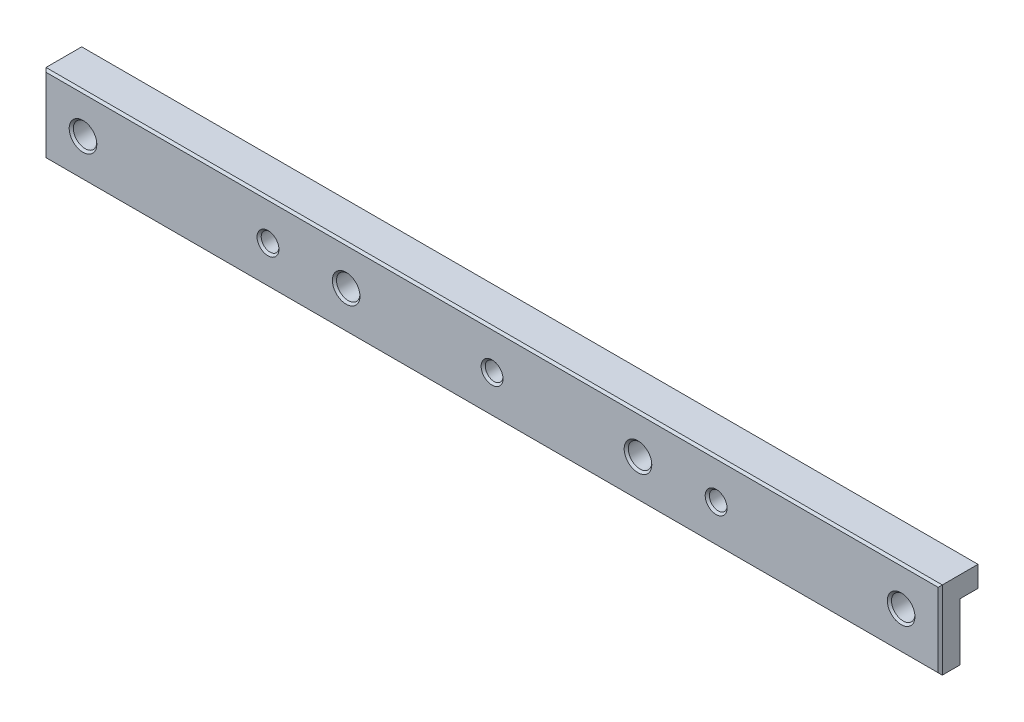
SolidWorks part; units mm, degrees
ref_plane "Front Plane" through (0, 0, 0) normal (0, 0, 1) x (1, 0, 0)
ref_plane "Top Plane" through (0, 0, 0) normal (0, 1, 0) x (1, 0, 0)
ref_plane "Right Plane" through (0, 0, 0) normal (1, 0, 0) x (0, 0, -1)
sketch "Sketch1" plane through (0, 0, 0) normal (0, 0, 1) x (1, 0, 0)
  line L0 (0, 7.5) -> (0, 0) construction
  line L1 (86, 7.5) -> (-86, 7.5)
  line L2 (86, 7.5) -> (86, 3.5)
  line L3 (86, -7.5) -> (-86, -7.5)
  line L4 (-86, 7.5) -> (-86, 3.5)
  line L5 (86, 3.5) -> (-86, 3.5)
  line L6 (-86, 3.5) -> (-86, -7.5)
  line L7 (86, 3.5) -> (86, -7.5)
  line L8 (0, 0) -> (0, -7.5) construction
  dimension "D1" = 172
  dimension "D2" = 7.5
  dimension "D3" = 4
extrude "Boss-Extrude1" add sketch "Sketch1" against normal blind 7.25 contours L7 L5 L6 L3 | L1 L0 L5 L2 | L0 L1 L4 L5 region at (0, 5.5, 0) region at (0, -2, 0)
extrude "Cut-Extrude1" cut sketch "Sketch1<6>" along normal blind 3.5 from surface contours L7 L5 L6 L3 region at (0, -2, 0) starting at face at (0, 0, -7.25)
sketch "Sketch1<6>" plane through (0, 0, 0) normal (0, 0, 1) x (1, 0, 0) same geometry as "Sketch1"
sketch "Sketch2" plane through (0, 0, 0) normal (0, 0, 1) x (1, 0, 0)
  line L0 (78.5, 0) -> (0, 0) construction
  line L1 (-86, 3.5) -> (-86, -7.5) construction
  line L2 (0, 0) -> (-78.5, 0) construction
  line L4 (-86, 0) -> (-43, 0) construction
  line L5 (-43, 0) -> (0, 0) construction
  line L6 (0, 0) -> (43, 0) construction
  line L7 (43, 0) -> (86, 0) construction
  circle A1 centre (-43, 0) radius 1.7
  circle A2 centre (0, 0) radius 1.7
  circle A3 centre (43, 0) radius 1.7
  circle A4 centre (-78.5, 0) radius 2.25
  circle A7 centre (78.5, 0) radius 2.25
  circle A10 centre (-28, 0) radius 2.25
  circle A11 centre (28, 0) radius 2.25
  dimension "D2" = 4.5
  dimension "D4" = 28
  dimension "D3" = 3.4
  dimension "D1" = 7.5
  dimension "D5" = 78.5
  dimension "D6" = 78.5
  dimension "D7" = 28
extrude "Cut-Extrude2" cut sketch "Sketch2" against normal through all both and the other way through all
chamfer "Chamfer1" distance 0.4 angle 45 11 edges at (0, -7.5, 0) (-86, 0, 0) (0, 7.5, 0) (86, 0, 0) (1.7, 0, 0) (30.25, 0, 0) (-25.75, 0, 0) (-41.3, 0, 0) (44.7, 0, 0) (-76.25, 0, 0) (80.75, 0, 0)
